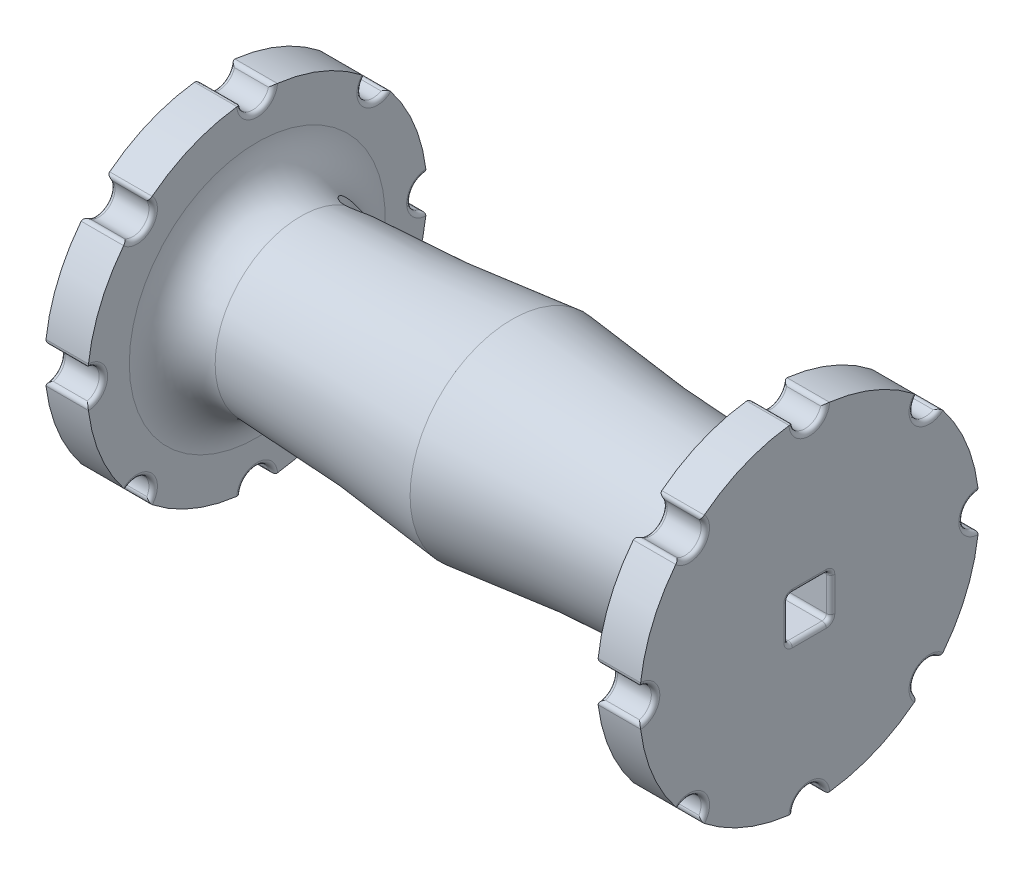
SolidWorks part; units mm, degrees
ref_plane "Front Plane" through (0, 0, 0) normal (0, 0, 1) x (1, 0, 0)
ref_plane "Top Plane" through (0, 0, 0) normal (0, 1, 0) x (1, 0, 0)
ref_plane "Right Plane" through (0, 0, 0) normal (1, 0, 0) x (0, 0, -1)
sketch "Sketch1" plane through (0, 0, 0) normal (0, 0, 1) x (1, 0, 0)
  line L0 (-44.45, 0) -> (44.45, 0)
  line L1 (44.45, 0) -> (44.45, 25.4)
  line L2 (44.45, 25.4) -> (38.1, 25.4)
  line L3 (38.1, 25.4) -> (38.1, 12.7)
  line L7 (0, 25.4) -> (0, 0) construction
  line L8 (0, 15.24) -> (0, 0) construction
  line L9 (-38.1, 25.4) -> (-38.1, 12.7)
  line L10 (-44.45, 25.4) -> (-38.1, 25.4)
  line L11 (-44.45, 0) -> (-44.45, 25.4)
  line L12 (0, 0) -> (93.4385, 0) construction
  arc A0 (38.1, 12.7) -> (0, 15.24) centre (38.1, 299.72) cw
  arc A1 (-38.1, 12.7) -> (0, 15.24) centre (-38.1, 299.72) ccw
  dimension "D1" = 38.1
  dimension "D2" = 25.4
  dimension "D3" = 12.7
  dimension "D4" = 44.45
  dimension "D5" = 15.24
revolve "Revolve1" add sketch "Sketch1" angle 360 about L12
fillet "Fillet1" radius 6.35 2 edges at (38.1, 0, 12.7) (-38.1, 0, 12.7)
sketch "Sketch2" plane through (-44.45, 0, 0) normal (-1, 0, 0) x (0, 0, 1)
  line L0 (0, 0) -> (0, 25.4) construction
  line L2 (-3.175, -3.175) -> (3.175, -3.175)
  line L3 (-3.175, -3.175) -> (-3.175, 3.175)
  line L4 (-3.175, 3.175) -> (3.175, 3.175)
  line L5 (3.175, -3.175) -> (3.175, 3.175)
  line L6 (-3.175, -3.175) -> (3.175, 3.175) construction
  line L7 (-3.175, 3.175) -> (3.175, -3.175) construction
  circle A0 centre (0, 0) radius 2.413 construction
  circle A1 centre (0, 0) radius 25.4 construction
  circle A3 centre (0, 25.4) radius 2.413
  circle A4 centre (17.9605, 17.9605) radius 2.413
  circle A5 centre (25.4, 0) radius 2.413
  circle A6 centre (17.9605, -17.9605) radius 2.413
  circle A7 centre (0, -25.4) radius 2.413
  circle A8 centre (-17.9605, -17.9605) radius 2.413
  circle A9 centre (-25.4, 0) radius 2.413
  circle A10 centre (-17.9605, 17.9605) radius 2.413
  point P3 (0, 12.7)
  point P7 (0, 25.4)
  point P26 (0, 0)
  dimension "D1" = 4.826
  dimension "D2" = 12.7
  dimension "D3" = 12.7
  dimension "D5" = 6.35
  dimension "D6" = 6.35
  dimension "D4" = 8
extrude "Cut-Extrude1" cut sketch "Sketch2" against normal through all
fillet "Fillet2" radius 0.635 76 edges at (38.1, 16.2543, -16.2543) (44.45, 16.2543, -16.2543) (38.1, 22.987, 0) (44.45, 22.987, 0) (38.1, 16.2543, 16.2543) (44.45, 16.2543, 16.2543) (38.1, 0, 22.987) (44.45, 0, 22.987) (38.1, -16.2543, 16.2543) (44.45, -16.2543, 16.2543) (38.1, -22.987, 0) (44.45, -22.987, 0) (38.1, -16.2543, -16.2543) (44.45, -16.2543, -16.2543) (38.1, 0, -22.987) (44.45, 0, -22.987) (-38.1, 16.2543, -16.2543) (-44.45, 16.2543, -16.2543) (-38.1, 22.987, 0) (-44.45, 22.987, 0) (-38.1, 16.2543, 16.2543) (-44.45, 16.2543, 16.2543) (-38.1, 0, 22.987) (-44.45, 0, 22.987) (-38.1, -16.2543, 16.2543) (-44.45, -16.2543, 16.2543) (-38.1, -22.987, 0) (-44.45, -22.987, 0) (-38.1, -16.2543, -16.2543) (-44.45, -16.2543, -16.2543) (-38.1, 0, -22.987) (-44.45, 0, -22.987) (44.45, 0, -3.175) (-44.45, 0, -3.175) (44.45, 3.175, 0) (0, 3.175, -3.175) (-44.45, 3.175, 0) (44.45, 0, 3.175) (0, 3.175, 3.175) (-44.45, 0, 3.175) (0, -3.175, -3.175) (44.45, -3.175, 0) (0, -3.175, 3.175) (-44.45, -3.175, 0) (41.275, 19.5838, -16.1751) (41.275, 16.1751, -19.5838) (41.275, 25.2854, 2.4103) (41.275, 25.2854, -2.4103) (41.275, 16.1751, 19.5838) (41.275, 19.5838, 16.1751) (41.275, -2.4103, 25.2854) (41.275, 2.4103, 25.2854) (41.275, -19.5838, 16.1751) (41.275, -16.1751, 19.5838) (41.275, -25.2854, -2.4103) (41.275, -25.2854, 2.4103) (41.275, -16.1751, -19.5838) (41.275, -19.5838, -16.1751) (41.275, 2.4103, -25.2854) (41.275, -2.4103, -25.2854) (-41.275, 19.5838, -16.1751) (-41.275, 16.1751, -19.5838) (-41.275, 25.2854, 2.4103) (-41.275, 25.2854, -2.4103) (-41.275, 16.1751, 19.5838) (-41.275, 19.5838, 16.1751) (-41.275, -2.4103, 25.2854) (-41.275, 2.4103, 25.2854) (-41.275, -19.5838, 16.1751) (-41.275, -16.1751, 19.5838) (-41.275, -25.2854, -2.4103) (-41.275, -25.2854, 2.4103) (-41.275, -16.1751, -19.5838) (-41.275, -19.5838, -16.1751) (-41.275, 2.4103, -25.2854) (-41.275, -2.4103, -25.2854)
sketch "Sketch3" plane through (0, 0, 0) normal (0, 1, 0) x (1, 0, 0)
  line L0 (0, 8.89) -> (-56.0709, 8.89) construction
  line L1 (-31.6063, -12.7735) -> (-31.6063, 12.7735) construction
  line L2 (0, 8.89) -> (0, 23.257) construction
  circle A0 centre (-31.6063, 8.89) radius 2.3283
  circle A1 centre (31.6063, 8.89) radius 2.3283
  point P3 (-31.6063, 8.89)
  point P7 (31.6063, 8.89)
  dimension "D1" = 4.6566
  dimension "D2" = 4.6566
  dimension "D3" = 8.89
extrude "Cut-Extrude2" cut sketch "Sketch3" against normal through all both and the other way through all
